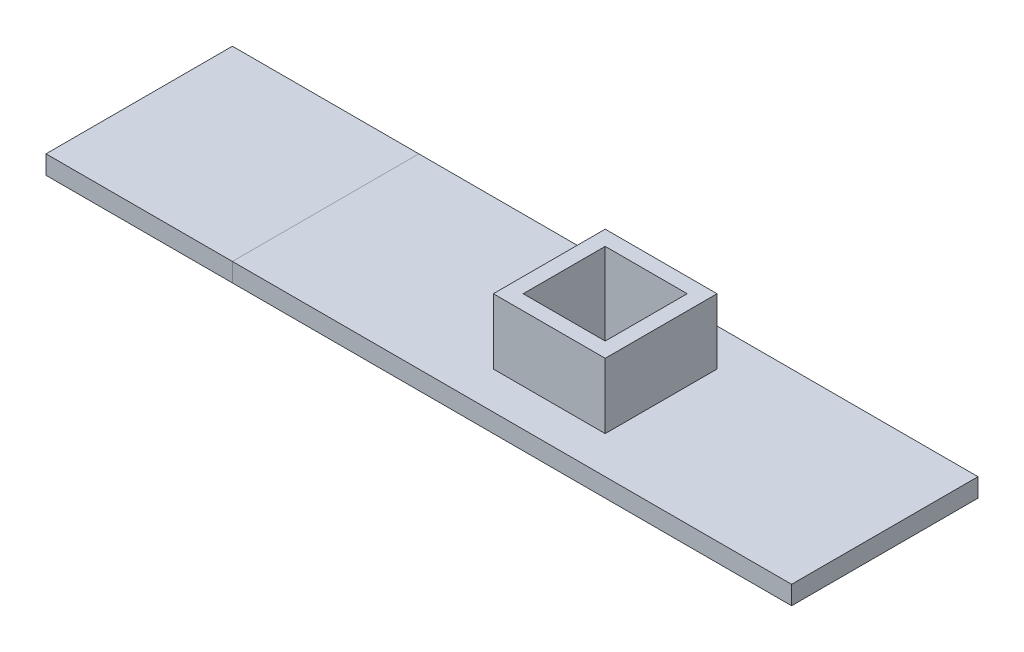
SolidWorks part; units mm, degrees
material "Silicon Dioxide"
ref_plane "Front Plane" through (0, 0, 0) normal (0, 0, 1) x (1, 0, 0)
ref_plane "Top Plane" through (0, 0, 0) normal (0, 1, 0) x (1, 0, 0)
ref_plane "Right Plane" through (0, 0, 0) normal (1, 0, 0) x (0, 0, -1)
sketch "Sketch1" plane through (0, 0, 0) normal (0, 1, 0) x (1, 0, 0)
  line L1 (-37.5, -12.5) -> (37.5, -12.5)
  line L2 (-37.5, -12.5) -> (-37.5, 12.5)
  line L3 (-37.5, 12.5) -> (37.5, 12.5)
  line L4 (37.5, -12.5) -> (37.5, 12.5)
  line L5 (-37.5, -12.5) -> (37.5, 12.5) construction
  line L6 (-37.5, 12.5) -> (37.5, -12.5) construction
  point P0 (0, 0)
  dimension "D1" = 25
  dimension "D2" = 75
extrude "Slide" add sketch "Sketch1" along normal mid plane 2.5
sketch "Sketch4" plane through (0, 0, 0) normal (0, 1, 0) x (1, 0, 0)
  line L1 (-37.5, 12.5) -> (-62.5, 12.5)
  line L2 (-37.5, 12.5) -> (-37.5, -12.5)
  line L3 (-37.5, -12.5) -> (-62.5, -12.5)
  line L4 (-62.5, 12.5) -> (-62.5, -12.5)
  dimension "D1" = 25
extrude "Label" add sketch "Sketch4" along normal mid plane 2.5 separate body
sketch "Sketch5" plane through (0, 0, 0) normal (0, 1, 0) x (1, 0, 0)
  line L1 (-5.5, -5.5) -> (5.5, -5.5)
  line L2 (-5.5, -5.5) -> (-5.5, 5.5)
  line L3 (-5.5, 5.5) -> (5.5, 5.5)
  line L4 (5.5, -5.5) -> (5.5, 5.5)
  line L5 (-5.5, -5.5) -> (5.5, 5.5) construction
  line L6 (-5.5, 5.5) -> (5.5, -5.5) construction
  line L7 (-7.5, -7.5) -> (7.5, -7.5)
  line L8 (-7.5, -7.5) -> (-7.5, 7.5)
  line L9 (-7.5, 7.5) -> (7.5, 7.5)
  line L10 (7.5, -7.5) -> (7.5, 7.5)
  line L11 (-7.5, -7.5) -> (7.5, 7.5) construction
  line L12 (-7.5, 7.5) -> (7.5, -7.5) construction
  point P0 (0, 0)
  point P6 (0, 0)
  dimension "D1" = 2
  dimension "D2" = 15
extrude "Boss-Extrude1" add sketch "Sketch5" along normal blind 10
sketch "Sketch6" plane through (0, 1.25, 0) normal (0, 1, 0) x (1, 0, 0)
  line L1 (-5.5, -5.5) -> (5.5, -5.5)
  line L2 (-5.5, -5.5) -> (-5.5, 5.5)
  line L3 (-5.5, 5.5) -> (5.5, 5.5)
  line L4 (5.5, -5.5) -> (5.5, 5.5)
  line L5 (-5.5, -5.5) -> (5.5, 5.5) construction
  line L6 (-5.5, 5.5) -> (5.5, -5.5) construction
  point P0 (0, 0)
extrude "Cut-Extrude1" cut sketch "Sketch6" against normal up to next (2.5 mm away)
